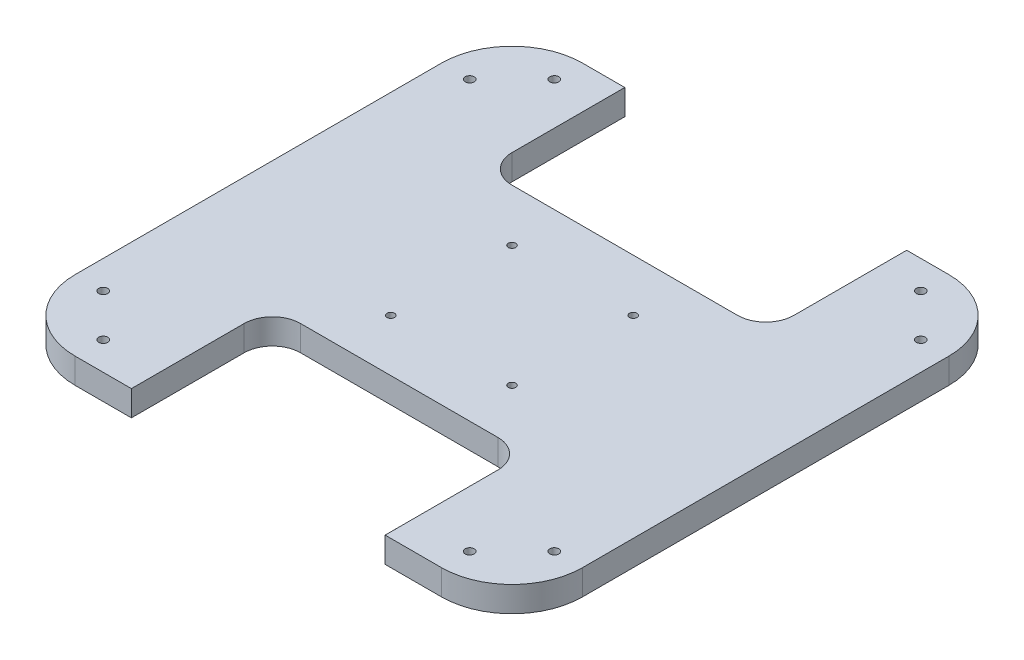
SolidWorks part; units mm, degrees
ref_plane "Front Plane" through (0, 0, 0) normal (0, 0, 1) x (1, 0, 0)
ref_plane "Top Plane" through (0, 0, 0) normal (0, 1, 0) x (1, 0, 0)
ref_plane "Right Plane" through (0, 0, 0) normal (1, 0, 0) x (0, 0, -1)
sketch "Sketch1" plane through (0, 0, 0) normal (0, 1, 0) x (1, 0, 0)
  line L1 (-65, -90) -> (65, -90)
  line L2 (-90, -65) -> (-90, 65)
  line L3 (-65, 90) -> (65, 90)
  line L4 (90, -65) -> (90, 65)
  arc A0 (-90, 65) -> (-65, 90) centre (-65, 65) cw
  arc A1 (65, 90) -> (90, 65) centre (65, 65) cw
  arc A2 (90, -65) -> (65, -90) centre (65, -65) cw
  arc A3 (-65, -90) -> (-90, -65) centre (-65, -65) cw
  point P4 (-90, 0)
  point P6 (0, 90)
  dimension "D3" = 25
  dimension "D1" = 180
  dimension "D2" = 180
extrude "Plate" add sketch "Sketch1" along normal blind 9
sketch "Sketch3" plane through (0, 9, 0) normal (0, 1, 0) x (1, 0, 0)
  line L0 (-65, 90) -> (-65, -90) construction
  line L1 (65, 90) -> (65, -90) construction
  line L2 (-90, 65) -> (90, 65) construction
  line L3 (-90, -65) -> (90, -65) construction
  circle A0 centre (-65, 80) radius 1.6
  circle A1 centre (-80, 65) radius 1.6
  circle A2 centre (80, 65) radius 1.6
  circle A3 centre (80, -65) radius 1.6
  circle A4 centre (65, 80) radius 1.6
  circle A5 centre (65, -80) radius 1.6
  circle A6 centre (-65, -80) radius 1.6
  circle A7 centre (-80, -65) radius 1.6
  dimension "D1" = 3.2
  dimension "D2" = 15
  dimension "D3" = 15
  dimension "D4" = 15
  dimension "D5" = 15
  dimension "D6" = 15
  dimension "D7" = 15
  dimension "D8" = 15
  dimension "D9" = 15
extrude "Hex Holes" cut sketch "Sketch3" against normal through all
sketch "Sketch4" plane through (0, 9, 0) normal (0, 1, 0) x (1, 0, 0)
  line L0 (-90, -65) -> (-90, 65) construction
  line L1 (-65, -90) -> (65, -90) construction
  circle A0 centre (-21.5, 21.5) radius 1.325
  circle A1 centre (21.5, 21.5) radius 1.325
  circle A2 centre (21.5, -21.5) radius 1.325
  circle A3 centre (-21.5, -21.5) radius 1.325
  dimension "D1" = 2.65
  dimension "D2" = 43
  dimension "D3" = 43
  dimension "D4" = 68.5
  dimension "D5" = 68.5
extrude "LiDAR Holes" cut sketch "Sketch4" against normal through all
sketch "Sketch5" plane through (0, 9, 0) normal (0, 1, 0) x (1, 0, 0)
  line L0 (-65, 90) -> (65, 90) construction
  line L1 (50, 90) -> (-50, 90)
  line L2 (50, 90) -> (50, 40)
  line L3 (50, 40) -> (-50, 40)
  line L4 (-50, 90) -> (-50, 40)
  line L5 (-65, -90) -> (65, -90) construction
  line L6 (45, -90) -> (-45, -90)
  line L7 (45, -90) -> (45, -40)
  line L8 (45, -40) -> (-45, -40)
  line L9 (-45, -90) -> (-45, -40)
  point P6 (0, 90)
  point P7 (0, 90)
  point P14 (0, -90)
  point P15 (0, -90)
  dimension "D1" = 100
  dimension "D2" = 50
  dimension "D3" = 50
  dimension "D4" = 90
extrude "Cut-Extrude1" cut sketch "Sketch5" against normal through all
sketch "Sketch6" plane through (0, 0, 0) normal (0, -1, 0) x (1, 0, 0)
  circle A0 centre (-21.5, 21.5) radius 3.5
  circle A1 centre (21.5, 21.5) radius 3.5
  circle A2 centre (-21.5, -21.5) radius 3.5
  circle A3 centre (21.5, -21.5) radius 3.5
  dimension "D1" = 7
extrude "Cut-Extrude2" cut sketch "Sketch6" against normal blind 5
fillet "Fillet1" radius 10 4 edges at (45, 4.5, 40) (-45, 4.5, 40) (50, 4.5, -40) (-50, 4.5, -40)
